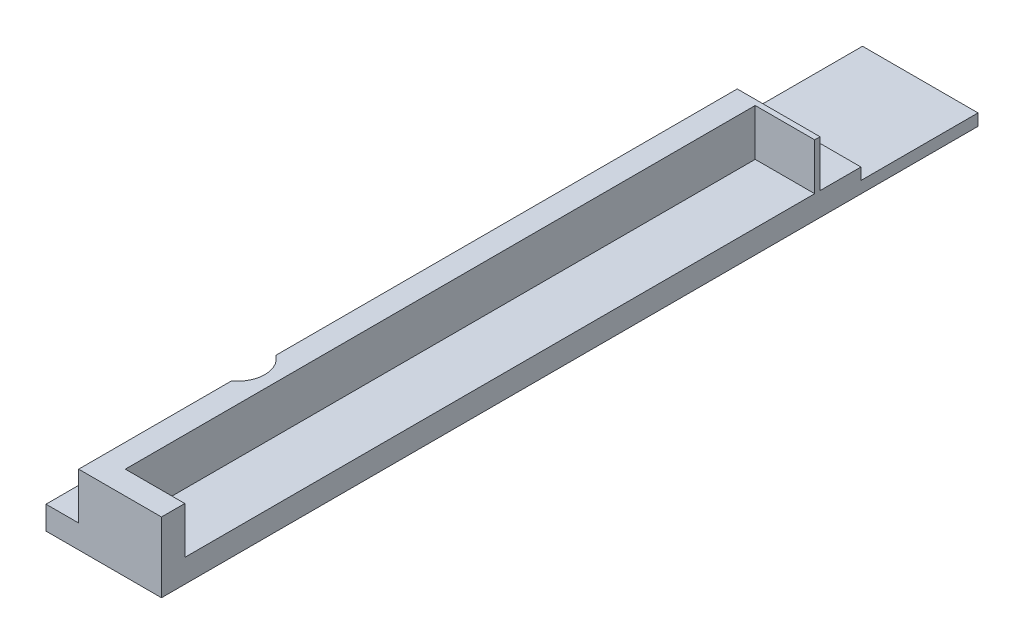
SolidWorks part; units mm, degrees
note: The reader was unsure of these and kept them because the rebuilt part matched: shared geometry of "Sketch6<3>".
ref_plane "Front Plane" through (0, 0, 0) normal (0, 0, 1) x (1, 0, 0)
ref_plane "Top Plane" through (0, 0, 0) normal (0, 1, 0) x (1, 0, 0)
ref_plane "Right Plane" through (0, 0, 0) normal (1, 0, 0) x (0, 0, -1)
sketch "Sketch1" plane through (0, 0, 0) normal (0, 1, 0) x (1, 0, 0)
  line L2 (-20.447, 54.1624) -> (-45.593, 54.1624)
  line L3 (-20.447, 54.1624) -> (-20.447, -123.6376)
  line L4 (-20.447, -123.6376) -> (-45.593, -123.6376)
  line L5 (-45.593, 54.1624) -> (-45.593, -123.6376)
  dimension "D1" = 25.146
  dimension "D3" = 177.8
extrude "Boss-Extrude1" add sketch "Sketch1" along normal blind 5.08
sketch "Sketch3" plane through (0, 5.08, 0) normal (0, 1, 0) x (1, 0, 0)
  line L0 (-33.401, -123.6376) -> (-33.401, 18.6024) construction
  line L1 (-45.593, -123.6376) -> (-20.447, -123.6376) construction
  line L3 (-20.447, -123.6376) -> (-20.447, 54.1624) construction
  line L4 (-38.481, 18.6024) -> (-20.447, 18.6024)
  line L5 (-20.447, -123.6376) -> (-33.401, -123.6376)
  line L6 (-20.447, -123.6376) -> (-20.447, -118.5576)
  line L7 (-20.447, -118.5576) -> (-33.401, -118.5576)
  line L8 (-33.401, -123.6376) -> (-33.401, -118.5576)
  line L9 (-33.401, -123.6376) -> (-38.481, -123.6376)
  line L10 (-33.401, -123.6376) -> (-33.401, 18.6024)
  line L11 (-33.401, 18.6024) -> (-38.481, 18.6024)
  line L12 (-38.481, -123.6376) -> (-38.481, 18.6024)
  line L13 (-38.481, 18.6024) -> (-33.401, 18.6024)
  line L17 (-38.481, 18.6024) -> (-38.481, 19.7686)
  line L18 (-38.481, 19.7686) -> (-20.447, 19.7686)
  line L19 (-20.447, 18.6024) -> (-20.447, 19.7686)
  dimension "D1" = 12.954
  dimension "D2" = 142.24
  dimension "D3" = 5.08
  dimension "D4" = 5.08
extrude "Boss-Extrude3" add sketch "Sketch3" along normal blind 10.16
sketch "Sketch4" plane through (0, 5.08, 0) normal (0, 1, 0) x (1, 0, 0)
  line L0 (-20.447, 19.7686) -> (-20.447, 54.1624) construction
  line L1 (-45.593, 54.1624) -> (-20.447, 54.1624)
  line L2 (-45.593, 54.1624) -> (-45.593, 28.6766)
  line L3 (-45.593, 28.6766) -> (-20.447, 28.6766)
  line L4 (-20.447, 54.1624) -> (-20.447, 28.6766)
extrude "Cut-Extrude1" cut sketch "Sketch4" against normal blind 2.54
sketch "Sketch5" plane through (0, 5.08, 0) normal (0, 1, 0) x (1, 0, 0)
  line L0 (-20.447, 19.7686) -> (-20.447, 28.6766) construction
  line L1 (-20.447, 24.2226) -> (-45.593, 24.2226) construction
  line L2 (-45.593, 28.6766) -> (-45.593, -123.6376) construction
  circle A0 centre (-33.02, 24.2226) radius 3
extrude "Cut-Extrude2" cut sketch "Sketch5" against normal through all
sketch "Sketch6" plane through (0, 5.08, 0) normal (0, 1, 0) x (1, 0, 0)
  line L0 (-42.037, -123.6376) -> (-42.037, 28.6766) construction
  line L1 (-45.593, -123.6376) -> (-38.481, -123.6376) construction
  line L2 (-45.593, 28.6766) -> (-20.447, 28.6766) construction
  circle A0 centre (-42.037, -85.5376) radius 3
  circle A1 centre (-42.037, -85.5376) radius 6
  dimension "D1" = 6
  dimension "D2" = 38.1
  dimension "D3" = 12
extrude "Cut-Extrude3" cut sketch "Sketch6" along normal blind 16.51 contours A0 | A1
extrude "Cut-Extrude4" cut sketch "Sketch6<3>" against normal through all contours L0 A0 | A0 L0
sketch "Sketch6<3>" plane through (0, 5.08, 0) normal (0, 1, 0) x (1, 0, 0) same geometry as "Sketch6"
